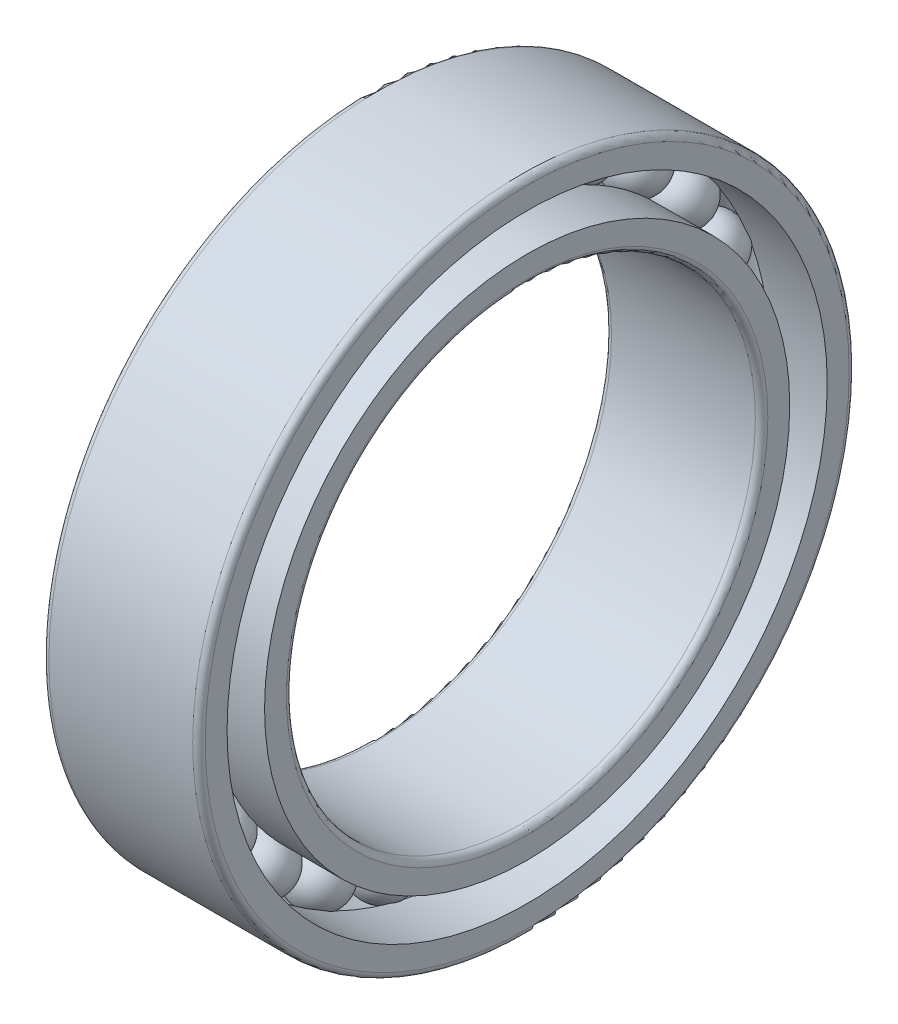
SolidWorks part; units mm, degrees
ref_plane "Plane1" through (0, 0, 0) normal (0, 0, 1) x (1, 0, 0)
ref_plane "Plane2" through (0, 0, 0) normal (0, 1, 0) x (1, 0, 0)
ref_plane "Plane3" through (0, 0, 0) normal (1, 0, 0) x (0, 0, -1)
sketch "Clipboard" plane through (0, 0, 0) normal (0, 0, 1) x (1, 0, 0)
  line L0 (-10, 0) -> (10, 0) construction
  line L1 (0, 0) -> (20.0976, -9.8023)
  line L2 (0, 0) -> (8.0891, 3.9453)
  line L3 (0, 0) -> (20.0976, -9.8023)
  line L4 (0, 0) -> (-22.3573, -0.3902)
  dimension "BallCLRad" = 9
sketch "CagSpiSke" plane through (0, 0, 0) normal (0, 0, 1) x (1, 0, 0)
  line L0 (0.09, 8.85) -> (0.09, 9.15)
  line L1 (0.09, 9.15) -> (-0.09, 9.15)
  line L2 (-0.09, 9.15) -> (-0.09, 8.85)
  line L3 (-0.09, 8.85) -> (0.09, 8.85)
  line L4 (-20.6375, 0) -> (20.6375, 0) construction
  line L5 (0, 0) -> (0, 23.7692) construction
  dimension "OD" = 18.3
  dimension "ID" = 17.7
revolve "CageSpine" add sketch "CagSpiSke" angle 0.001 about L4 reverse direction yes
ref_axis "Axis1" through (-50, 0, 0) along (1, 0, 0)
sketch "CagBalSke" plane through (0, 0, 0) normal (0, 0, 1) x (1, 0, 0)
  line L0 (-0.99, 9) -> (0.99, 9)
  line L1 (-1.905, 9) -> (1.905, 9) construction
  line L2 (-10, 0) -> (10, 0) construction
  line L3 (0, 0) -> (0, 24) construction
  arc A0 (0.99, 9) -> (-0.99, 9) centre (0, 9) cw
  dimension "BallCLRad" = 9
revolve "CageBall" [suppressed] add sketch "CagBalSke" angle 360 about L1 reverse direction yes
pattern_circular "CageBalls" [suppressed] count 26 every 13.846 about axis through (-50, 0, 0) along (1, 0, 0)
sketch "CagTrmODSke" plane through (0, 0, 0) normal (0, 0, 1) x (1, 0, 0)
  line L0 (0.991, 9.15) -> (0.991, 9.991)
  line L1 (0.991, 9.991) -> (-0.991, 9.991)
  line L2 (-0.991, 9.991) -> (-0.991, 9.15)
  line L3 (-0.991, 9.15) -> (0.991, 9.15)
  line L4 (-20.6375, 0) -> (20.6375, 0) construction
  line L5 (0, 0) -> (0, 25) construction
  dimension "Width" = 1.982
  dimension "ID" = 18.3
  dimension "OD" = 19.982
revolve "CageTrimOD" [suppressed] cut sketch "CagTrmODSke" angle 360 about L4 reverse direction yes
sketch "CagTrmIDSke" plane through (0, 0, 0) normal (0, 0, 1) x (1, 0, 0)
  line L0 (0.991, 8.011) -> (0.991, 8.85)
  line L1 (0.991, 8.85) -> (-0.991, 8.85)
  line L2 (-0.991, 8.85) -> (-0.991, 8.011)
  line L3 (-0.991, 8.011) -> (0.991, 8.011)
  line L4 (-20.6375, 0) -> (20.6375, 0) construction
  line L5 (0, 0) -> (0, 25) construction
  dimension "Width" = 1.982
  dimension "ID" = 16.022
  dimension "OD" = 17.7
revolve "CageTrimID" [suppressed] cut sketch "CagTrmIDSke" angle 360 about L4 reverse direction yes
sketch "BalSimSke" plane through (0, 0, 0) normal (0, 0, 1) x (1, 0, 0)
  line L0 (-10, 0) -> (10, 0) construction
  line L1 (-10, 9) -> (10, 9) construction
  line L2 (0, 0) -> (0, 23) construction
  circle A0 centre (0, 9) radius 0.9
  dimension "BallCLRad" = 9
  dimension "Ball_diameter" = 1.8
revolve "BallsSimplified" [suppressed] add sketch "BalSimSke" angle 360 about L0
sketch "BalDetSke" plane through (0, 0, 0) normal (0, 0, 1) x (1, 0, 0)
  line L0 (-0.9, 9) -> (0.9, 9)
  line L1 (-1.905, 9) -> (1.905, 9) construction
  line L2 (0, 0) -> (0, 25) construction
  arc A0 (0.9, 9) -> (-0.9, 9) centre (0, 9) cw
  dimension "BallCLRad" = 9
  dimension "Ball_diameter" = 1.8
revolve "BallDetailed" add sketch "BalDetSke" angle 360 about L1 reverse direction yes
sketch "InnRacSke" plane through (0, 0, 0) normal (0, 0, 1) x (1, 0, 0)
  line L0 (-0.6369, 8.4) -> (-2.5, 8.4)
  line L1 (-2.5, 8.4) -> (-2.5, 7.7)
  line L2 (-2.3, 7.5) -> (2.3, 7.5)
  line L3 (2.5, 7.7) -> (2.5, 8.4)
  line L4 (2.5, 8.4) -> (0.6369, 8.4)
  line L5 (-20.6375, 0) -> (20.6375, 0) construction
  line L6 (0, 0) -> (0, 30) construction
  arc A0 (-2.5, 7.7) -> (-2.3, 7.5) centre (-2.3, 7.7) ccw
  arc A1 (2.3, 7.5) -> (2.5, 7.7) centre (2.3, 7.7) ccw
  arc A2 (0.6369, 8.4) -> (-0.6369, 8.4) centre (0, 9) cw
  dimension "BallCLRad" = 9
  dimension "Fillet_radius" = 0.2
  dimension "Ball_diameter" = 1.75
  dimension "ID" = 15
  dimension "OD" = 16.8
  dimension "Width" = 5
revolve "InnerRace" add sketch "InnRacSke" angle 360 about L5 reverse direction yes
sketch "OutRacSke" plane through (0, 0, 0) normal (0, 0, 1) x (1, 0, 0)
  line L0 (-0.6369, 9.6) -> (-2.5, 9.6)
  line L1 (-2.5, 9.6) -> (-2.5, 10.3)
  line L2 (-2.3, 10.5) -> (2.3, 10.5)
  line L3 (2.5, 10.3) -> (2.5, 9.6)
  line L4 (2.5, 9.6) -> (0.6369, 9.6)
  line L5 (-20.6375, 0) -> (20.6375, 0) construction
  line L6 (0, 0) -> (0, 30) construction
  arc A0 (-2.5, 10.3) -> (-2.3, 10.5) centre (-2.3, 10.3) cw
  arc A1 (2.3, 10.5) -> (2.5, 10.3) centre (2.3, 10.3) cw
  arc A2 (0.6369, 9.6) -> (-0.6369, 9.6) centre (0, 9) ccw
  dimension "BallCLRad" = 9
  dimension "Fillet_radius" = 0.2
  dimension "Ball_diameter" = 1.75
  dimension "Width" = 5
revolve "OuterRace" add sketch "OutRacSke" angle 360 about L5 reverse direction yes
pattern_circular "BallsDetailed" count 26 every 13.846 about axis through (-50, 0, 0) along (1, 0, 0) of "BallDetailed"
equation "\"BallCLRad@Clipboard\" = ( \"OD@OutRacSke\" + \"ID@InnRacSke\" ) / 4"
equation "\"BallCLRad@BalSimSke\" = \"BallCLRad@Clipboard\""
equation "\"BallCLRad@BalDetSke\" = \"BallCLRad@Clipboard\""
equation "\"BallCLRad@InnRacSke\" = \"BallCLRad@Clipboard\""
equation "\"BallCLRad@OutRacSke\" = \"BallCLRad@Clipboard\""
equation "\"Ball_diameter@InnRacSke\" = \"Ball_diameter@BalDetSke\" - 0.05"
equation "\"Ball_diameter@OutRacSke\" = \"Ball_diameter@BalDetSke\" - 0.05"
equation "\"Ball_diameter@BalSimSke\" = \"Ball_diameter@BalDetSke\""
equation "\"Width@OutRacSke\" = \"Width@InnRacSke\""
equation "\"Fillet_radius@OutRacSke\" = \"Fillet_radius@InnRacSke\""
equation "\"Max_count@Clipboard\" = int( 3.14159265 / atn(( \"Ball_diameter@BalDetSke\" / 2) / sqr( \"BallCLRad@Clipboard\"  *  \"BallCLRad@Clipboard\" - ( \"Ball_diameter@BalDetSke\" / 2) *  ( \"Ball_diameter@BalDetSke\" / 2))))"
equation "\"Max_count@Clipboard\" = ((sgn( \"Max_count@Clipboard\" - \"Count@Clipboard\" )-1)*( \"Max_count@Clipboard\" - \"Count@Clipboard\" ))/-2+ \"Count@Clipboard\""
equation "\"Count@BallsDetailed\" = int( \"Show_count@Clipboard\" ) "
equation "\"Count@BallsDetailed\" = ((sgn( \"Count@BallsDetailed\" - \"Max_count@Clipboard\" )-1)*( \"Count@BallsDetailed\" - \"Max_count@Clipboard\" ))/-2+ \"Max_count@Clipboard\""
equation "\"Count@BallsDetailed\" = ((sgn( \"Count@BallsDetailed\" - \"Min_count@Clipboard\" )+1)*( \"Count@BallsDetailed\" - \"Min_count@Clipboard\"))/2 +\"Min_count@Clipboard\""
equation "\"Angle@BallsDetailed\" = 360.0 / \"Max_count@Clipboard\""
equation "\"BallCLRad@CagBalSke\" = \"BallCLRad@Clipboard\""
equation "\"Count@CageBalls\" = \"Count@BallsDetailed\""
equation "\"Angle@CageBalls\" = \"Angle@BallsDetailed\""
equation "\"Angle@CageSpine\" =  \"Angle@CageBalls\" * ( \"Count@CageBalls\" -1 + int( \"Count@CageBalls\" / \"Max_count@Clipboard\" ) )  + 0.001 -  int( \"Count@CageBalls\" / \"Max_count@Clipboard\" ) * 0.001"
equation "\"Angle@CageSpine\" =  \"Angle@CageSpine\" * int( \"Min_count@Clipboard\" / 2) + int(1 / \"Min_count@Clipboard\")  * 0.001"
equation "\"CageWallOD@CagBalSke\" =  \"Ball_diameter@BalDetSke\" * 1.1"
equation "\"Thickness@CagSpiSke\" =  \"Ball_diameter@BalDetSke\" * 0.1"
equation "\"OD@CagTrmODSke\" = \"BallCLRad@Clipboard\" * 2 + \"CageWallOD@CagBalSke\" + 0.002"
equation "\"ID@CagTrmODSke\" = \"BallCLRad@Clipboard\" * 2 + \"Ball_diameter@BalDetSke\" / 6"
equation "\"OD@CagTrmIDSke\" = \"BallCLRad@Clipboard\" * 2 - \"Ball_diameter@BalDetSke\" / 6"
equation "\"ID@CagTrmIDSke\" = \"BallCLRad@Clipboard\" * 2 - \"CageWallOD@CagBalSke\" + 0.002"
equation "\"OD@CagSpiSke\" = \"ID@CagTrmODSke\""
equation "\"ID@CagSpiSke\" = \"OD@CagTrmIDSke\""
equation "\"Width@CagTrmODSke\" = \"CageWallOD@CagBalSke\" + 0.002"
equation "\"Width@CagTrmIDSke\" = \"CageWallOD@CagBalSke\" + 0.002"
